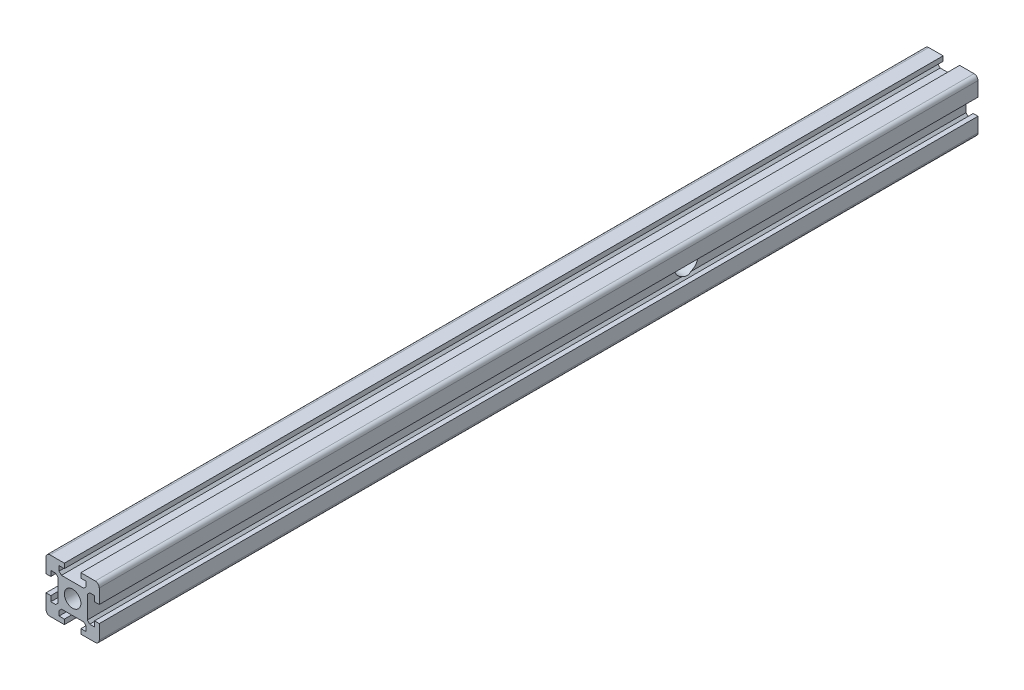
SolidWorks part; units mm, degrees
material "6061 Alloy"
ref_plane "Front Plane" through (0, 0, 0) normal (0, 0, 1) x (1, 0, 0)
ref_plane "Top Plane" through (0, 0, 0) normal (0, 1, 0) x (1, 0, 0)
ref_plane "Right Plane" through (0, 0, 0) normal (1, 0, 0) x (0, 0, -1)
sketch "Sketch1" plane through (0, 0, 0) normal (0, 0, 1) x (1, 0, 0)
  line L0 (-10, 3.1) -> (-8.2, 3.1)
  line L1 (-8.5, 10) -> (-3.1, 10) construction
  line L2 (-10, 8.5) -> (-10, 3.1) construction
  line L3 (-10, -3.1) -> (-10, -8.5) construction
  line L4 (-8.5, -10) -> (-3.1, -10) construction
  line L5 (-10, -3.1) -> (-10, -8.5)
  line L6 (-8.5, -10) -> (-3.1, -10)
  line L7 (-8.2, 3.1) -> (-8.2, 5.1)
  line L8 (-8.2, 5.1) -> (-6.4, 5.1)
  line L9 (-10, -3.1) -> (-8.2, -3.1)
  line L10 (-8.2, -3.1) -> (-8.2, -5.1)
  line L11 (-8.2, -5.1) -> (-6.4, -5.1)
  line L13 (-6.4, 5.1) -> (-5.4929, 4.1929)
  line L14 (-5.4929, 4.1929) -> (-5.4929, -4.1929)
  line L15 (-6.4, -5.1) -> (-5.4929, -4.1929)
  line L16 (-3.1, 10) -> (-3.1, 8.2)
  line L17 (-3.1, 8.2) -> (-5.1, 8.2)
  line L19 (-5.1, 8.2) -> (-5.1, 6.4)
  line L20 (-5.1, 6.4) -> (-4.1929, 5.4929)
  line L21 (-4.1929, 5.4929) -> (4.1929, 5.4929)
  line L22 (4.1929, 5.4929) -> (5.1, 6.4)
  line L23 (5.1, 6.4) -> (5.1, 8.2)
  line L24 (5.1, 8.2) -> (3.1, 8.2)
  line L25 (3.1, 8.2) -> (3.1, 10)
  line L26 (-3.1, -10) -> (-3.1, -8.2)
  line L27 (-3.1, -8.2) -> (-5.1, -8.2)
  line L28 (-5.1, -8.2) -> (-5.1, -6.4)
  line L29 (-5.1, -6.4) -> (-4.1929, -5.4929)
  line L30 (-4.1929, -5.4929) -> (4.1929, -5.4929)
  line L31 (4.1929, -5.4929) -> (5.1, -6.4)
  line L32 (5.1, -6.4) -> (5.1, -8.2)
  line L33 (5.1, -8.2) -> (3.1, -8.2)
  line L34 (3.1, -8.2) -> (3.1, -10)
  line L35 (3.1, -10) -> (8.5, -10)
  line L36 (10, -8.5) -> (10, -3.1)
  line L37 (10, -3.1) -> (8.2, -3.1)
  line L38 (8.2, -3.1) -> (8.2, -5.1)
  line L39 (8.2, -5.1) -> (6.4, -5.1)
  line L40 (6.4, -5.1) -> (5.4929, -4.1929)
  line L41 (5.4929, -4.1929) -> (5.4929, 4.1929)
  line L42 (5.4929, 4.1929) -> (6.4, 5.1)
  line L43 (6.4, 5.1) -> (8.2, 5.1)
  line L44 (8.2, 5.1) -> (8.2, 3.1)
  line L45 (8.2, 3.1) -> (10, 3.1)
  line L46 (10, 3.1) -> (10, 8.5)
  line L47 (8.5, 10) -> (3.1, 10)
  line L48 (-3.1, 10) -> (-8.5, 10)
  line L49 (-10, 8.5) -> (-10, 3.1)
  arc A0 (-8.5, 10) -> (-10, 8.5) centre (-8.5, 8.5) ccw
  arc A1 (-10, -8.5) -> (-8.5, -10) centre (-8.5, -8.5) ccw construction
  arc A2 (8.5, -10) -> (10, -8.5) centre (8.5, -8.5) ccw
  arc A3 (8.5, 10) -> (10, 8.5) centre (8.5, 8.5) cw
  arc A4 (-8.5, -10) -> (-10, -8.5) centre (-8.5, -8.5) cw
  circle A6 centre (0, 0) radius 3.1
  point P0 (0, 0)
  point P44 (-5.2, -3.4858)
  point P47 (-5.2, 3.4858)
  dimension "D3" = 5.4929
  dimension "D5" = 1.5
  dimension "D1" = 6.2
  dimension "D2" = 5.4929
  dimension "D4" = 1.5
  dimension "D6" = 1.5
extrude "Boss-Extrude1" add sketch "Sketch1" along normal blind 330
sketch "Sketch5" plane through (-5.4929, 0, 0) normal (-1, 0, 0) x (0, 0, -1)
  line L2 (-330, 10) -> (0, 10) construction
  circle A0 centre (-105, 0) radius 4.5
  dimension "D1" = 9
  dimension "D2" = 105
  dimension "D3" = 10
extrude "Cut-Extrude2" cut sketch "Sketch5" against normal blind 12 and the other way through all
